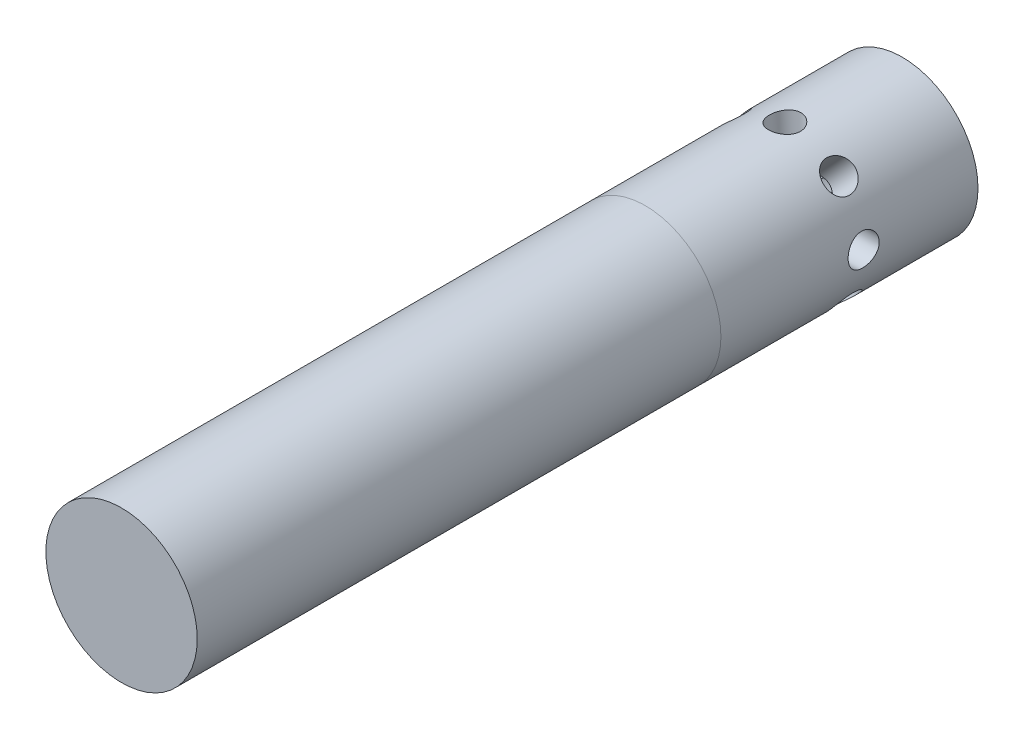
SolidWorks part; units mm, degrees
ref_plane "Front Plane" through (0, 0, 0) normal (0, 0, 1) x (1, 0, 0)
ref_plane "Top Plane" through (0, 0, 0) normal (0, 1, 0) x (1, 0, 0)
ref_plane "Right Plane" through (0, 0, 0) normal (1, 0, 0) x (0, 0, -1)
sketch "Sketch1" plane through (0, 0, 0) normal (0, 0, 1) x (1, 0, 0)
  circle A0 centre (0, 0) radius 19.875
  dimension "D1" = 39.75
extrude "Boss-Extrude1" add sketch "Sketch1" against normal blind 205
sketch "Sketch3" plane through (0, 0, -205) normal (0, 0, -1) x (-1, 0, 0)
  circle A0 centre (0, 0) radius 10
  dimension "D1" = 20
extrude "Cut-Extrude1" cut sketch "Sketch3" against normal blind 50
sketch "Sketch4" plane through (0, 0, -205) normal (0, 0, -1) x (-1, 0, 0)
  circle A0 centre (0, 0) radius 19.875 construction
  point P0 (-0.8422, -19.8571)
ref_plane "Plane1" through (0.8422, -19.8571, -205) normal (0.0424, -0.9991, 0) x (-0.9991, -0.0424, 0)
sketch "Sketch6" plane through (0.8422, -19.8571, -205) normal (0.0424, -0.9991, 0) x (-0.9991, -0.0424, 0)
  line L0 (0, -30) -> (0, 0) construction
  line L1 (19.875, 0) -> (-19.875, 0) construction
  circle A0 centre (0, -30) radius 4.0759
  dimension "D1" = 30
extrude "Cut-Extrude2" cut sketch "Sketch6" against normal blind 10
pattern_circular "CirPattern1" count 8 over 360 about axis through (0, 0, -205) along (0, 0, 1) of "Cut-Extrude2" reverse direction yes
sketch "Sketch7" plane through (0, 0, 0) normal (0, -1, 0) x (1, 0, 0)
  line L0 (0, -197.5) -> (0, -137.5) construction
  line L2 (19.875, -137.5) -> (-19.875, -137.5)
  line L3 (-19.875, 0) -> (-19.875, -171.0122) construction
  line L4 (85, -197.5) -> (-85, -197.5) construction
  point P10 (0, -137.5)
  dimension "D1" = 60
split "Split2" trim tools "Sketch7" bodies to split 104 resulting bodies 107 108
